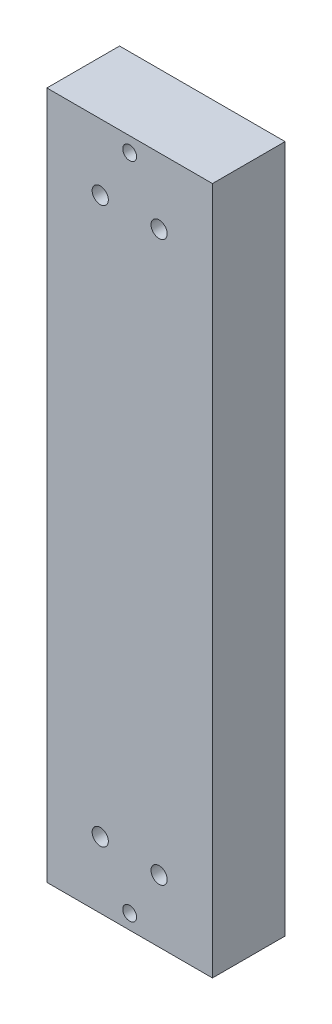
SolidWorks part; units mm, degrees
ref_plane "Front Plane" through (0, 0, 0) normal (0, 0, 1) x (1, 0, 0)
ref_plane "Top Plane" through (0, 0, 0) normal (0, 1, 0) x (1, 0, 0)
ref_plane "Right Plane" through (0, 0, 0) normal (1, 0, 0) x (0, 0, -1)
sketch "Sketch1" plane through (0, 0, 0) normal (0, 0, 1) x (1, 0, 0)
  line L1 (-6.5, -85.5) -> (6.5, -85.5)
  line L2 (-6.5, -85.5) -> (-6.5, 85.5)
  line L3 (-6.5, 85.5) -> (6.5, 85.5)
  line L4 (6.5, -85.5) -> (6.5, 85.5)
  line L5 (6.5, -84.5) -> (6.5, 84.5) construction
  line L6 (6.5, -85.5) -> (9.5, 85.5) construction
  line L7 (9.5, -85.5) -> (22.5, -85.5)
  line L8 (9.5, -85.5) -> (9.5, 85.5)
  line L9 (9.5, 85.5) -> (22.5, 85.5)
  line L10 (22.5, -85.5) -> (22.5, 85.5)
  line L11 (-14.5, -85.5) -> (30.5, -85.5)
  line L12 (-14.5, -93.5) -> (30.5, -93.5)
  line L13 (-14.5, -93.5) -> (-14.5, 93.5)
  line L14 (-14.5, 93.5) -> (30.5, 93.5)
  line L15 (30.5, -93.5) -> (30.5, 93.5)
  line L16 (-14.5, -93.5) -> (30.5, 93.5) construction
  line L17 (-14.5, 93.5) -> (30.5, -93.5) construction
  line L18 (-14.5, 85.5) -> (30.5, 85.5)
  line L19 (-12.5, -85.5) -> (-12.5, 85.5)
  line L20 (28.5, -85.5) -> (28.5, 85.5)
  line L21 (8, -93.5) -> (8, -85.5) construction
  line L22 (30.5, 0) -> (-14.5, 0) construction
  line L24 (-6.5, 84.5) -> (6.5, 84.5) construction
  line L25 (22.5, -84.5) -> (22.5, 84.5) construction
  line L26 (-6.5, -84.5) -> (-6.5, 84.5) construction
  line L27 (9.5, -84.5) -> (9.5, 84.5) construction
  line L28 (-6.5, -84.5) -> (6.5, -84.5) construction
  circle A0 centre (0, -75.5) radius 2.2
  circle A1 centre (16, -76.5) radius 2.2
  circle A2 centre (0, 75.5) radius 2.2
  circle A3 centre (16, 75.5) radius 2.2
  circle A4 centre (8, -89.5) radius 1.875
  circle A5 centre (8, 89.5) radius 1.875
  point P26 (8, 0)
  dimension "D3" = 3.75
  dimension "D8" = 4.4
  dimension "D1" = 8
  dimension "D2" = 8
  dimension "D4" = 2
  dimension "D5" = 2
  dimension "D6" = 1
  dimension "D7" = 1
extrude "Boss-Extrude1" add sketch "Sketch1" along normal blind 4.75 contours A2 | A3 | A0 | A1 | L13 L14 L15 L12 | A5 | A4 region at (0, -75.5, 0) region at (16, -76.5, 0) region at (0, 75.5, 0) region at (16, 75.5, 0)
extrude "Boss-Extrude2" add sketch "Sketch1<3>" against normal offset from surface (15 mm away) 2 contours L13 L18 L3 L9 L15 L14 A5 | L11 L19 L18 L13 | L12 L15 L11 L7 L1 L13 A4 | L20 L11 L15 L18 | L18 L4 L11 L8 region at (0, -85.9571, 0) region at (8, 0, 0) region at (-9.5, 85.9571, 0) region at (-13.5, 0, 0) region at (29.5, 0, 0) offset beyond the face yes
sketch "Sketch1<3>" plane through (0, 0, 0) normal (0, 0, 1) x (1, 0, 0) same geometry as "Sketch1"
equation "\"D5@Sketch1\"=\"D4@Sketch1\""
